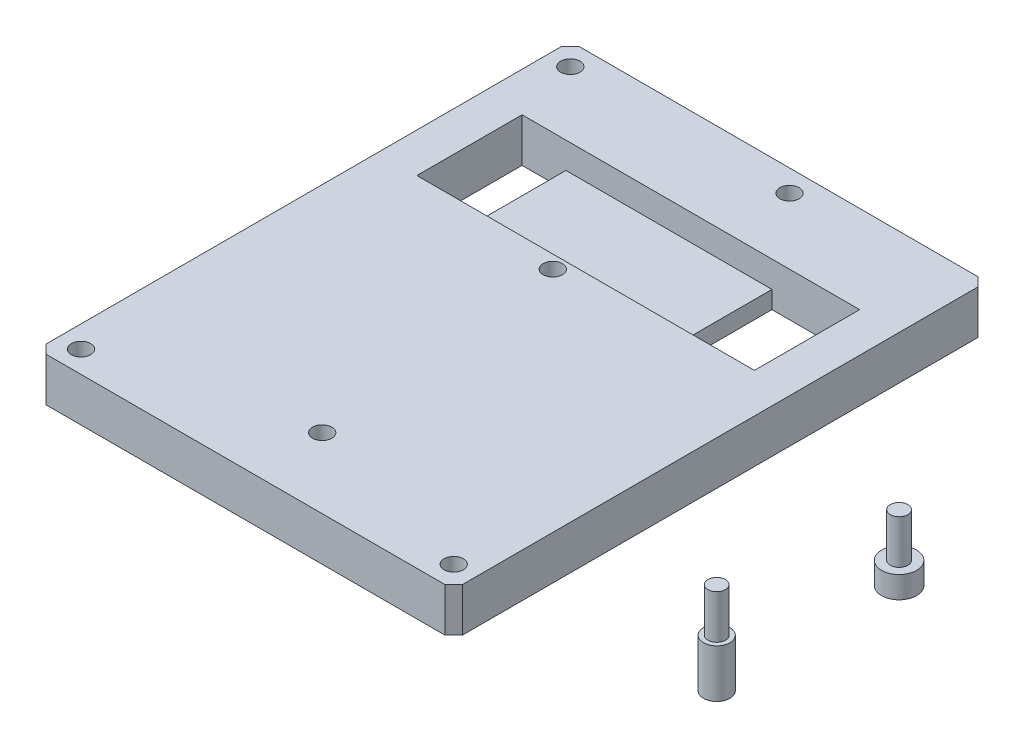
SolidWorks part; units mm, degrees
ref_plane "前视基准面" through (0, 0, 0) normal (0, 0, 1) x (1, 0, 0)
ref_plane "上视基准面" through (0, 0, 0) normal (0, 1, 0) x (1, 0, 0)
ref_plane "右视基准面" through (0, 0, 0) normal (1, 0, 0) x (0, 0, -1)
other "Configuration Table"
sketch "草图1" plane through (0, 0, 0) normal (0, 1, 0) x (1, 0, 0)
  line L1 (-54.4053, 33.3382) -> (-6.9053, 33.3382)
  line L2 (-54.4053, 33.3382) -> (-54.4053, -27.4618)
  line L3 (-54.4053, -27.4618) -> (-6.9053, -27.4618)
  line L4 (-6.9053, 33.3382) -> (-6.9053, -27.4618)
  line L5 (-54.4053, 33.3382) -> (-49.4053, 33.3382) construction
  line L6 (-54.4053, 33.3382) -> (-54.4053, 23.3382) construction
  dimension "D1" = 47.5
  dimension "D2" = 60.8
extrude "凸台-拉伸1" add sketch "草图1" against normal blind 5 contours L4 L3 L2 L1
sketch "草图2" plane through (0, 0, 0) normal (0, 1, 0) x (1, 0, 0)
  line L0 (-54.4053, 33.3382) -> (-54.4053, -27.4618) construction
  line L1 (-49.9053, 23.3382) -> (-11.4053, 23.3382)
  line L2 (-49.9053, 23.3382) -> (-49.9053, 11.3382)
  line L3 (-49.9053, 11.3382) -> (-11.4053, 11.3382)
  line L4 (-11.4053, 23.3382) -> (-11.4053, 11.3382)
  line L5 (-54.4053, 33.3382) -> (-6.9053, 33.3382) construction
  dimension "D1" = 4.5
  dimension "D2" = 10
  dimension "D3" = 12
  dimension "D4" = 38.5
extrude "切除-拉伸1" cut sketch "草图2" against normal blind 3 contours L2 L3 L4 L1
sketch "草图3" plane through (0, -3, 0) normal (0, 1, 0) x (1, 0, 0)
  line L0 (-49.9053, 11.3382) -> (-11.4053, 11.3382) construction
  line L3 (-49.9053, 23.3382) -> (-44.9053, 23.3382)
  line L4 (-49.9053, 23.3382) -> (-49.9053, 11.3382)
  line L5 (-49.9053, 11.3382) -> (-44.9053, 11.3382)
  line L6 (-44.9053, 23.3382) -> (-44.9053, 11.3382)
  line L7 (-49.9053, 11.3382) -> (-11.4053, 11.3382) construction
  line L8 (-11.4053, 23.3382) -> (-21.4053, 23.3382)
  line L9 (-11.4053, 23.3382) -> (-11.4053, 11.3382)
  line L10 (-11.4053, 11.3382) -> (-21.4053, 11.3382)
  line L11 (-21.4053, 23.3382) -> (-21.4053, 11.3382)
  dimension "D1" = 5
  dimension "D2" = 10
extrude "切除-拉伸2" cut sketch "草图3" against normal blind 2
sketch "草图4" plane through (0, 0, 0) normal (0, 1, 0) x (1, 0, 0)
  line L0 (-6.9053, 33.3382) -> (-6.9053, -27.4618) construction
  line L3 (-54.4053, -27.4618) -> (-6.9053, -27.4618) construction
  line L4 (-54.4053, 33.3382) -> (-54.4053, -27.4618) construction
  line L5 (-54.4053, 33.3382) -> (-6.9053, 33.3382) construction
  circle A0 centre (-9.4053, -24.9618) radius 1.1
  circle A1 centre (-51.9053, -24.9618) radius 1.1
  circle A2 centre (-51.9053, 30.8382) radius 1.1
  circle A3 centre (-26.9053, 30.8382) radius 1.1
  dimension "D1" = 2.5
  dimension "D3" = 2.5
  dimension "D5" = 2.5
  dimension "D7" = 20
  dimension "D2" = 2.5
  dimension "D4" = 2.5
  dimension "D6" = 2.5
  dimension "D8" = 2.5
extrude "切除-拉伸3" cut sketch "草图4" against normal blind 5
sketch "草图5" plane through (0, -5, 0) normal (0, -1, 0) x (1, 0, 0)
  line L0 (-6.9053, -33.3382) -> (-6.9053, 27.4618) construction
  line L2 (-54.4053, 27.4618) -> (-6.9053, 27.4618) construction
  line L3 (-54.4053, -33.3382) -> (-6.9053, -33.3382) construction
  circle A0 centre (13.0947, -3.3382) radius 2
  circle A1 centre (13.0947, 17.4618) radius 1.5
  dimension "D1" = 20
  dimension "D2" = 20
  dimension "D3" = 10
  dimension "D4" = 30
extrude "凸台-拉伸2" add sketch "草图5" against normal blind 2.5 separate body contours A0 region at (13.0947, -5, -3.3382)
extrude "凸台-拉伸3" add sketch "草图5<3>" against normal blind 5.5 separate body contours A1 region at (13.0947, -5, 17.4618)
sketch "草图5<3>" plane through (0, -5, 0) normal (0, -1, 0) x (1, 0, 0) same geometry as "草图5"
sketch "草图6" plane through (0, 0, 0) normal (0, 1, 0) x (1, 0, 0)
  line L0 (-54.4053, 33.3382) -> (-6.9053, 33.3382) construction
  line L1 (-54.4053, 33.3382) -> (-54.4053, -27.4618) construction
  circle A0 centre (-32.9053, 9.8382) radius 1.1
  dimension "D1" = 23.5
  dimension "D2" = 21.5
extrude "切除-拉伸4" cut sketch "草图6" against normal blind 5
sketch "草图7" plane through (0, -2.5, 0) normal (0, 1, 0) x (1, 0, 0)
  circle A0 centre (13.0947, 3.3382) radius 1
extrude "凸台-拉伸4" add sketch "草图7" along normal blind 5
sketch "草图8" plane through (0, 0.5, 0) normal (0, 1, 0) x (1, 0, 0)
  circle A0 centre (13.0947, -17.4618) radius 1
extrude "凸台-拉伸5" add sketch "草图8" along normal blind 5
sketch "草图9" plane through (0, 0, 0) normal (0, 1, 0) x (1, 0, 0)
  line L0 (-6.9053, 33.3382) -> (-6.9053, -27.4618) construction
  line L1 (-54.4053, -27.4618) -> (-6.9053, -27.4618) construction
  circle A0 centre (-29.9053, -19.4618) radius 1.1
  dimension "D1" = 23
  dimension "D2" = 8
extrude "切除-拉伸5" cut sketch "草图9" against normal blind 5
chamfer "倒角1" distance 1 angle 45 4 edges at (-54.4053, -2.5, 27.4618) (-54.4053, -2.5, -33.3382) (-6.9053, -2.5, -33.3382) (-6.9053, -2.5, 27.4618)
